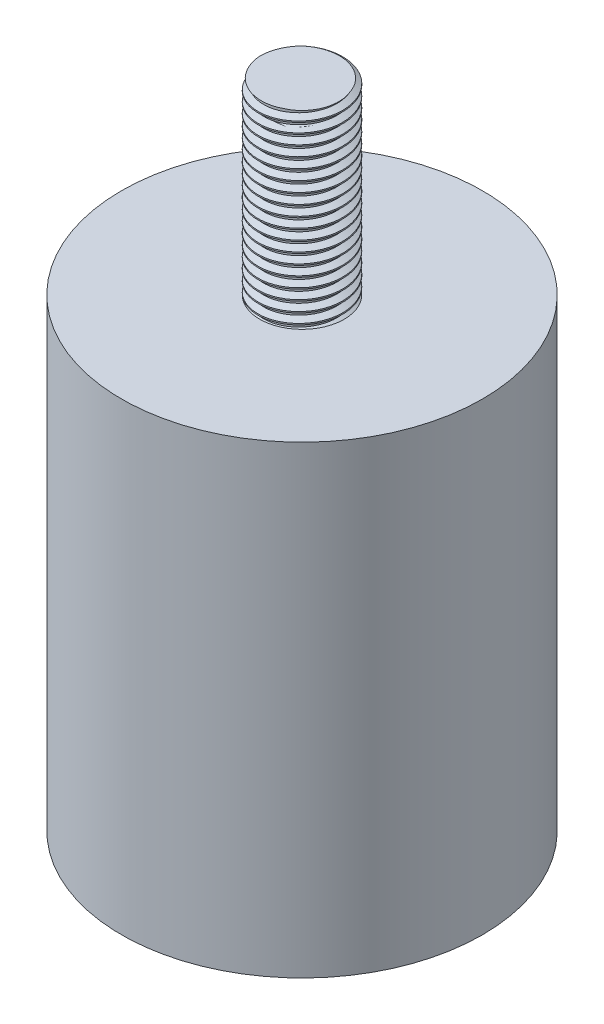
SolidWorks part; units mm, degrees
ref_plane "Ön Düzlem" through (0, 0, 0) normal (0, 0, 1) x (1, 0, 0)
ref_plane "Üst Düzlem" through (0, 0, 0) normal (0, 1, 0) x (1, 0, 0)
ref_plane "Sağ Düzlem" through (0, 0, 0) normal (1, 0, 0) x (0, 0, -1)
sketch "Sketch1" plane through (0, 0, 0) normal (0, 0, 1) x (1, 0, 0)
  line L1 (-17.5, 22.5) -> (0, 22.5)
  line L2 (-17.5, 22.5) -> (-17.5, -22.5)
  line L3 (-17.5, -22.5) -> (0, -22.5)
  line L4 (0, 22.5) -> (0, -22.5)
  line L5 (0, 22.5) -> (-4.1, 22.5)
  line L6 (0, 22.5) -> (0, 40.5)
  line L7 (0, 40.5) -> (-4.1, 40.5)
  line L8 (-4.1, 22.5) -> (-4.1, 40.5)
  point P4 (0, 0)
  dimension "D1" = 17.5
  dimension "D2" = 45
  dimension "D3" = 4.1
  dimension "D4" = 18
revolve "Revolve1" add sketch "Sketch1" angle 360 about L4 region at (-8.75, 0, 0) region at (-2.05, 31.5, 0)
thread "Thread1" pitch 1 method cut profile "Thread Profile1" start angle 0, offset 1, length 0, pitch 1, diameter 8.2
ref_plane "Plane1" through (-4.1, 41.5, 0) normal (0, 0, 1) x (-1, 0, 0)
sketch "Thread Profile1" plane through (-4.1, 41.5, 0) normal (0, 0, 1) x (-1, 0, 0)
  line L0 (0, 0) -> (0, 1) construction
  line L11 (0, 0) -> (0, 0.875)
  line L12 (0, 0.875) -> (-0.5413, 0.5625)
  line L13 (-0.5413, 0.5625) -> (-0.5413, 0.3125)
  line L15 (-0.5413, 0.3125) -> (0, 0)
  line L17 (-0.5413, 0.4375) -> (0, 0.4375) construction
  point P2 (0, 0)
  dimension "Pitch" = 1
  dimension "Profile_Angle" = 60
  dimension "Profile_Land" = 0.25
  dimension "Profile_Height" = 0.5413
hole_wizard "M8 Tapped Hole1" positions "Sketch6" profile "Sketch7" tap size "M8" standard "ISO"
sketch "Sketch6" plane through (0, -22.5, 0) normal (0, -1, 0) x (-1, 0, 0)
  point P0 (0, 0)
sketch "Sketch7" plane through (0, -22.5, 0) normal (1, 0, 0) x (0, 0, -1)
  line L0 (0, 0) -> (0, 17.0429)
  line L1 (0, 17.0429) -> (3.4, 15)
  line L2 (3.4, 15) -> (3.4, 0)
  line L5 (3.4, 0) -> (0, 0)
  line L10 (0, 17.0429) -> (-3.4, 15) construction
  line L11 (0, -6.35) -> (0, 107.95) construction
  dimension "Tap Drill Dia." = 6.8
  dimension "Tap Drill Depth" = 15
  dimension "Drill Angle" = 118
cosmetic thread "Hole Thread1" parameters "D1"=12, "D2"=8
